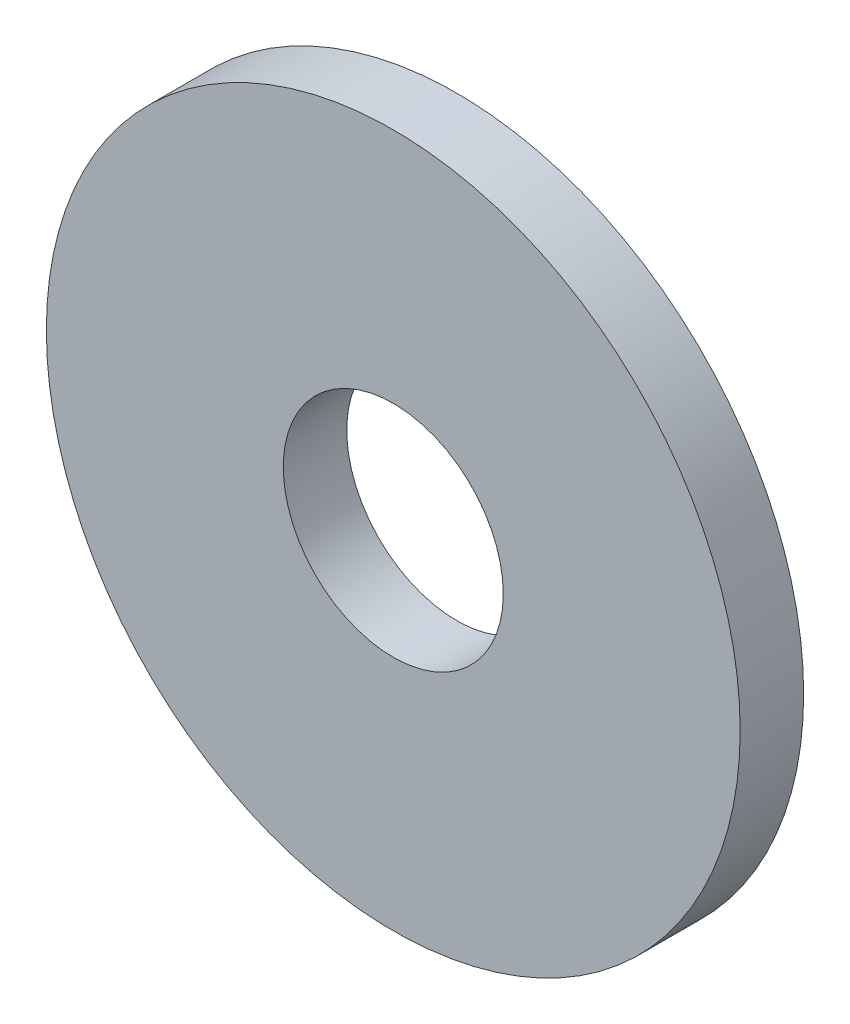
SolidWorks part; units mm, degrees
ref_plane "Přední rovina" through (0, 0, 0) normal (0, 0, 1) x (1, 0, 0)
ref_plane "Horní rovina" through (0, 0, 0) normal (0, 1, 0) x (1, 0, 0)
ref_plane "Pravá rovina" through (0, 0, 0) normal (1, 0, 0) x (0, 0, -1)
sketch "Skica1" plane through (0, 0, 0) normal (0, 0, 1) x (1, 0, 0)
  circle A0 centre (0, 0) radius 5.2
  circle A1 centre (0, 0) radius 16.4
  dimension "D1" = 10.4
  dimension "D2" = 32.8
extrude "Přidat vysunutím1" add sketch "Skica1" along normal blind 3
